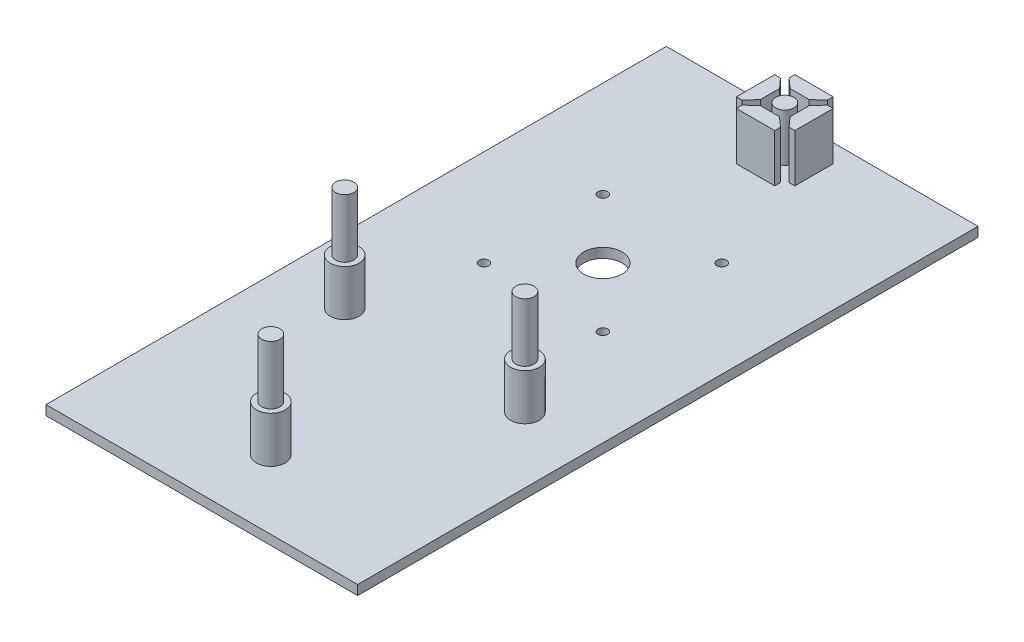
SolidWorks part; units mm, degrees
note: The reader was unsure of these and kept them because the rebuilt part matched: shared geometry of "Sketch7<3>".
ref_plane "Front Plane" through (0, 0, 0) normal (0, 0, 1) x (1, 0, 0)
ref_plane "Top Plane" through (0, 0, 0) normal (0, 1, 0) x (1, 0, 0)
ref_plane "Right Plane" through (0, 0, 0) normal (1, 0, 0) x (0, 0, -1)
sketch "Sketch1" plane through (0, 0, 0) normal (0, 1, 0) x (1, 0, 0)
  line L0 (62.103, -37.272) -> (62.103, -42.352)
  line L1 (0, 0) -> (82.55, 0)
  line L2 (0, 0) -> (0, -164.338)
  line L3 (0, -164.338) -> (82.55, -164.338)
  line L4 (82.55, 0) -> (82.55, -164.338)
  line L5 (62.103, -58.1) -> (62.103, -37.272)
  line L6 (62.103, -42.352) -> (57.023, -42.352)
  line L9 (51.275, 0) -> (31.275, 0)
  line L11 (62.103, -37.272) -> (20.447, -37.272)
  line L12 (62.103, -37.272) -> (62.103, -78.928)
  line L13 (62.103, -78.928) -> (20.447, -78.928)
  line L14 (20.447, -37.272) -> (20.447, -78.928)
  line L15 (41.275, -58.1) -> (82.55, -58.1)
  line L16 (41.275, -58.1) -> (41.275, -37.272)
  line L17 (41.275, -58.1) -> (20.447, -58.1)
  circle A7 centre (41.275, -58.1) radius 5.08
  circle A11 centre (57.023, -42.352) radius 1.27
  circle A15 centre (57.023, -73.848) radius 1.27
  circle A16 centre (25.527, -73.848) radius 1.27
  circle A17 centre (25.527, -42.352) radius 1.27
  point P26 (39.8836, -58.1)
  point P30 (41.275, -58.1)
  dimension "D4" = 5.08
  dimension "D6" = 41.275
  dimension "D9" = 20.828
  dimension "D3" = 5.08
  dimension "D5" = 4
  dimension "D1" = 82.55
  dimension "D2" = 164.338
  dimension "D7" = 41.656
  dimension "D8" = 20.828
extrude "base extrude" add sketch "Sketch1" along normal blind 2.54
sketch "Sketch6" plane through (0, 2.54, 0) normal (0, 1, 0) x (1, 0, 0)
  line L0 (46.355, -16.129) -> (43.815, -13.843)
  line L1 (0, 0) -> (82.55, 0) construction
  line L2 (41.275, -17.653) -> (46.355, -17.653)
  line L3 (45.212, -9.906) -> (45.212, -7.366)
  line L4 (45.212, -9.906) -> (45.212, -12.446)
  line L5 (46.355, -17.653) -> (46.355, -16.129)
  line L6 (49.022, -9.906) -> (49.022, -4.826)
  line L7 (49.022, -9.906) -> (49.022, -14.986)
  line L8 (49.022, -4.826) -> (47.498, -4.826)
  line L9 (47.498, -4.826) -> (45.212, -7.366)
  line L10 (49.022, -14.986) -> (47.498, -14.986)
  line L11 (47.498, -14.986) -> (45.212, -12.446)
  line L12 (41.275, 0) -> (51.181, 0)
  line L13 (41.275, -13.843) -> (43.815, -13.843)
  line L14 (51.181, 0) -> (31.369, 0)
  line L15 (51.181, 0) -> (51.181, -19.812)
  line L16 (51.181, -19.812) -> (31.369, -19.812)
  line L17 (31.369, 0) -> (31.369, -19.812)
  line L18 (41.275, -13.843) -> (38.735, -13.843)
  line L19 (36.195, -16.129) -> (38.735, -13.843)
  line L20 (36.195, -17.653) -> (36.195, -16.129)
  line L21 (41.275, -17.653) -> (36.195, -17.653)
  line L22 (35.052, -14.986) -> (37.338, -12.446)
  line L23 (33.528, -9.906) -> (33.528, -14.986)
  line L24 (33.528, -14.986) -> (35.052, -14.986)
  line L25 (37.338, -9.906) -> (37.338, -12.446)
  line L26 (37.338, -9.906) -> (37.338, -7.366)
  line L27 (35.052, -4.826) -> (37.338, -7.366)
  line L28 (33.528, -4.826) -> (35.052, -4.826)
  line L29 (33.528, -9.906) -> (33.528, -4.826)
  line L30 (36.195, -3.683) -> (38.735, -5.969)
  line L31 (41.275, -2.159) -> (36.195, -2.159)
  line L32 (36.195, -2.159) -> (36.195, -3.683)
  line L33 (41.275, -5.969) -> (38.735, -5.969)
  line L34 (41.275, -5.969) -> (43.815, -5.969)
  line L35 (46.355, -3.683) -> (43.815, -5.969)
  line L36 (46.355, -2.159) -> (46.355, -3.683)
  line L37 (41.275, -2.159) -> (46.355, -2.159)
  circle A0 centre (41.275, -9.906) radius 2.413
  point P44 (41.275, -9.906)
  dimension "D1" = 4
extrude "middle bar holder" add sketch "Sketch6" along normal blind 12.7 contours L29 L23 L24 L22 L25 L26 L27 L28 | A0 | L37 L31 L32 L30 L33 L34 L35 L36 | L11 L10 L7 L6 L8 L9 L3 L4 | L21 L2 L5 L0 L13 L18 L19 L20
sketch "Sketch7" plane through (0, 2.54, 0) normal (0, 1, 0) x (1, 0, 0)
  line L2 (0, -164.338) -> (82.55, -164.338) construction
  line L7 (17.399, -114.554) -> (65.151, -114.554)
  circle A0 centre (41.275, -146.05) radius 11.938
  circle A1 centre (41.275, -146.05) radius 2.413
  circle A2 centre (65.151, -102.616) radius 11.938
  circle A3 centre (17.399, -102.616) radius 11.938
  circle A4 centre (65.151, -102.616) radius 2.413
  circle A5 centre (17.399, -102.616) radius 2.413
  circle A6 centre (41.275, -146.05) radius 3.81
  circle A7 centre (65.151, -102.616) radius 3.81
  circle A8 centre (17.399, -102.616) radius 3.81
  dimension "D2" = 9.525
  dimension "D4" = 19.558
  dimension "D1" = 9.525
  dimension "D3" = 23.876
  dimension "D5" = 9.525
  dimension "D7" = 6.35
  dimension "D6" = 47.752
extrude "Boss-Extrude6" add sketch "Sketch7" along normal blind 27.686 contours A5 | A1 | A4
extrude "Boss-Extrude7" add sketch "Sketch7<3>" along normal blind 12.192 contours A6 A1 | A7 A4 | A8 A5
sketch "Sketch7<3>" plane through (0, 2.54, 0) normal (0, 1, 0) x (1, 0, 0) same geometry as "Sketch7"
